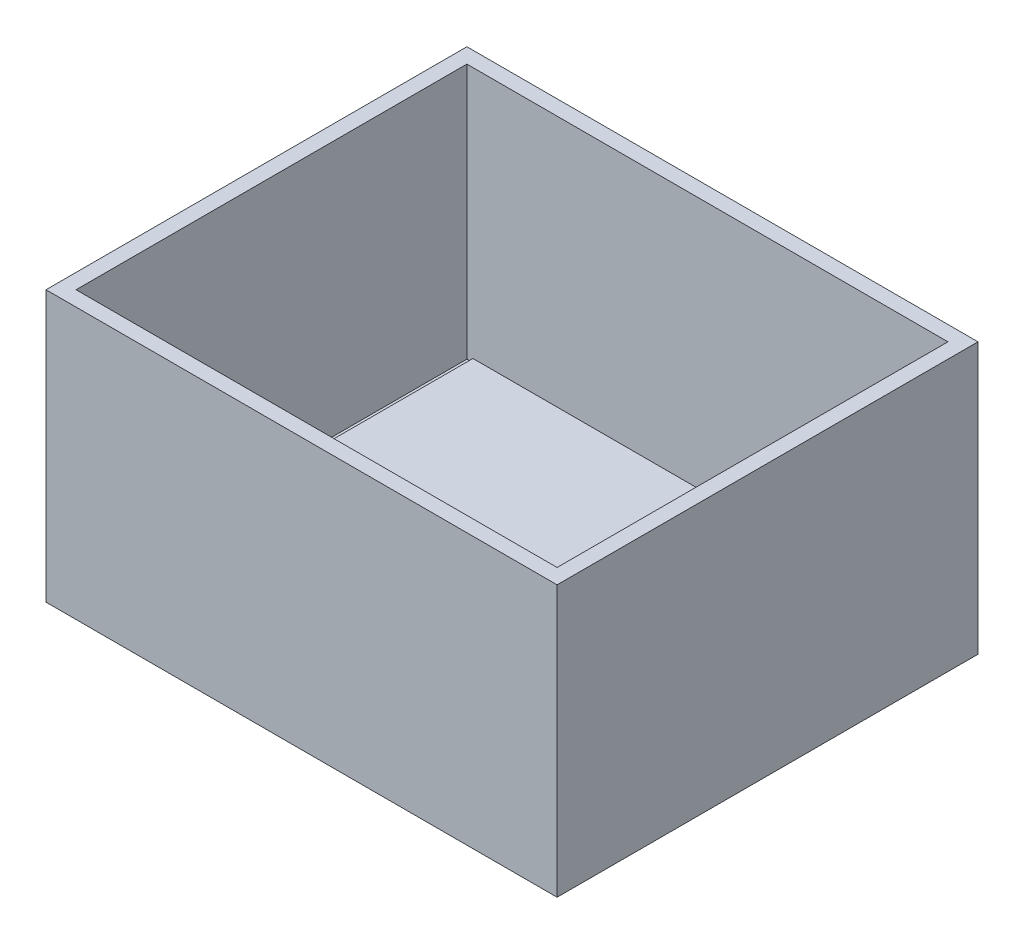
SolidWorks part; units mm, degrees
ref_plane "Front Plane" through (0, 0, 0) normal (0, 0, 1) x (1, 0, 0)
ref_plane "Top Plane" through (0, 0, 0) normal (0, 1, 0) x (1, 0, 0)
ref_plane "Right Plane" through (0, 0, 0) normal (1, 0, 0) x (0, 0, -1)
other "Configuration Table"
sketch "Sketch1" plane through (0, 0, 0) normal (1, 0, 0) x (0, 0, -1)
  line L1 (-45, 0) -> (-115, 0)
  line L2 (-45, 0) -> (-45, 45)
  line L3 (-45, 45) -> (-115, 45)
  line L4 (-115, 0) -> (-115, 45)
  line L5 (-45, 0) -> (-115, 45) construction
  line L6 (-45, 45) -> (-115, 0) construction
  point P0 (-80, 22.5)
extrude "enclosure" add sketch "Sketch1" along normal blind 85 from offset 165 separate body
sketch "Sketch2" plane through (0, 0, 0) normal (1, 0, 0) x (0, 0, -1)
  line L1 (-47.5, 2.5) -> (-112.5, 2.5)
  line L2 (-47.5, 2.5) -> (-47.5, 50)
  line L3 (-47.5, 50) -> (-112.5, 50)
  line L4 (-112.5, 2.5) -> (-112.5, 50)
  line L5 (-47.5, 2.5) -> (-112.5, 50) construction
  line L6 (-47.5, 50) -> (-112.5, 2.5) construction
  point P0 (-80, 26.25)
extrude "cavity" add sketch "Sketch2" along normal blind 80 from offset 167.5 separate body
combine bodies "Combine1" operation type subtract main body 102 bodies to subtract 103
sketch "Sketch3" plane through (0, 0, 0) normal (1, 0, 0) x (0, 0, -1)
  line L1 (-52, 6) -> (-105.4, 6)
  line L2 (-52, 6) -> (-52, 7.6)
  line L3 (-52, 7.6) -> (-105.4, 7.6)
  line L4 (-105.4, 6) -> (-105.4, 7.6)
  line L5 (-52, 6) -> (-105.4, 7.6) construction
  line L6 (-52, 7.6) -> (-105.4, 6) construction
  point P0 (-78.7, 6.8)
extrude "arduino_uno" add sketch "Sketch3" along normal blind 68.6 from offset 173 separate body
